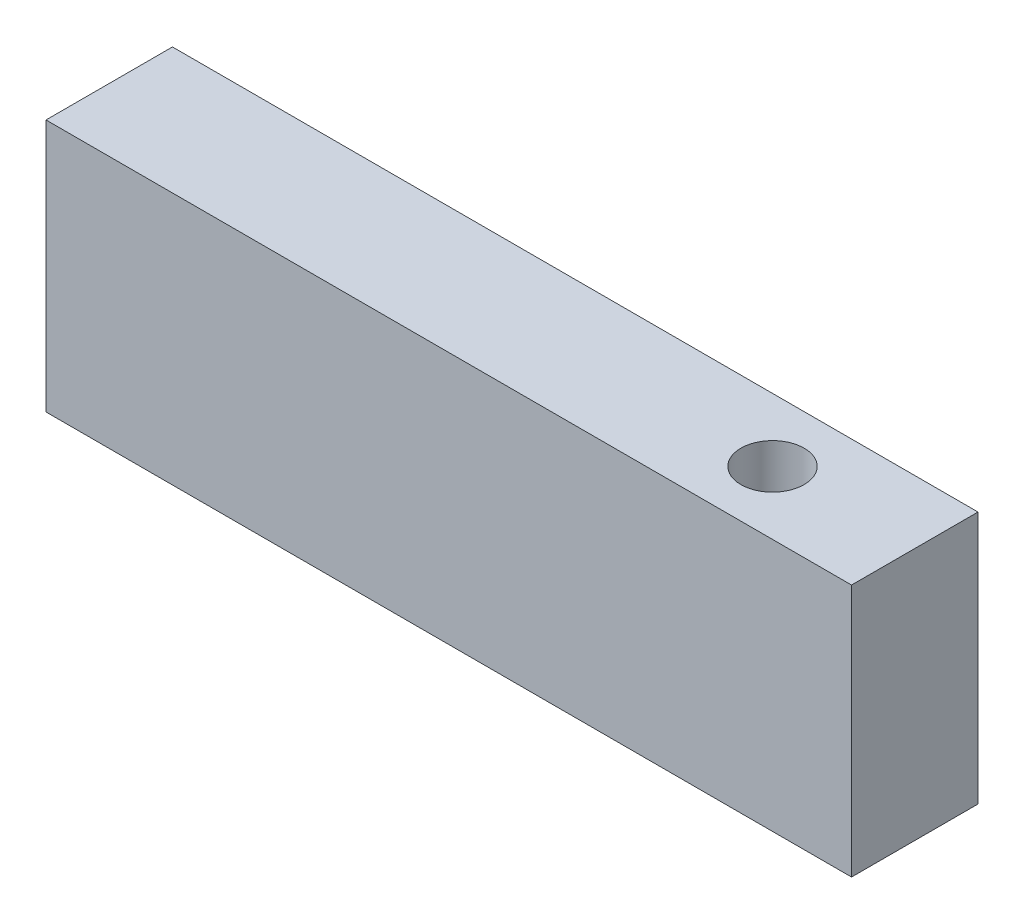
SolidWorks part; units mm, degrees
ref_plane "Front Plane" through (0, 0, 0) normal (0, 0, 1) x (1, 0, 0)
ref_plane "Top Plane" through (0, 0, 0) normal (0, 1, 0) x (1, 0, 0)
ref_plane "Right Plane" through (0, 0, 0) normal (1, 0, 0) x (0, 0, -1)
sketch "Sketch1" plane through (0, 0, 0) normal (0, 0, 1) x (1, 0, 0)
  line L1 (0, 0) -> (161.798, 0)
  line L2 (0, 0) -> (0, 50.8)
  line L3 (0, 50.8) -> (161.798, 50.8)
  line L4 (161.798, 0) -> (161.798, 50.8)
  dimension "D1" = 161.798
  dimension "D2" = 50.8
extrude "Boss-Extrude1" add sketch "Sketch1" along normal blind 25.4
sketch "Sketch2" plane through (0, 50.8, 0) normal (0, 1, 0) x (1, 0, 0)
  line L0 (161.798, -25.4) -> (161.798, 0) construction
  line L1 (161.798, -25.4) -> (0, -25.4) construction
  circle A0 centre (133.223, -12.7) radius 6.35
  dimension "D3" = 12.7
  dimension "D1" = 28.575
  dimension "D2" = 12.7
extrude "Cut-Extrude1" cut sketch "Sketch2" against normal blind 381
